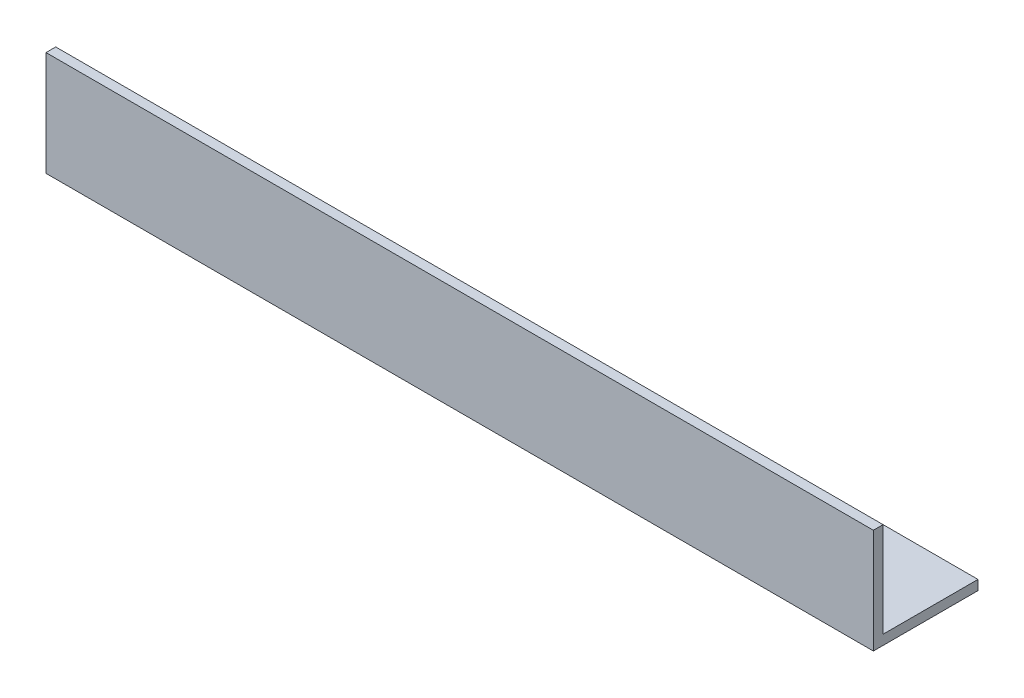
SolidWorks part; units mm, degrees
ref_plane "Спереди" through (0, 0, 0) normal (0, 0, 1) x (1, 0, 0)
ref_plane "Сверху" through (0, 0, 0) normal (0, 1, 0) x (1, 0, 0)
ref_plane "Справа" through (0, 0, 0) normal (1, 0, 0) x (0, 0, -1)
sketch "Эскиз1" plane through (0, 0, 0) normal (1, 0, 0) x (0, 0, -1)
  line L0 (0, 43) -> (0, 0)
  line L1 (0, 0) -> (43, 0)
extrude "Вытянуть-Тонкостенный1" add sketch "Эскиз1" along normal blind 340 thin thin type one direction reverse wall 4
